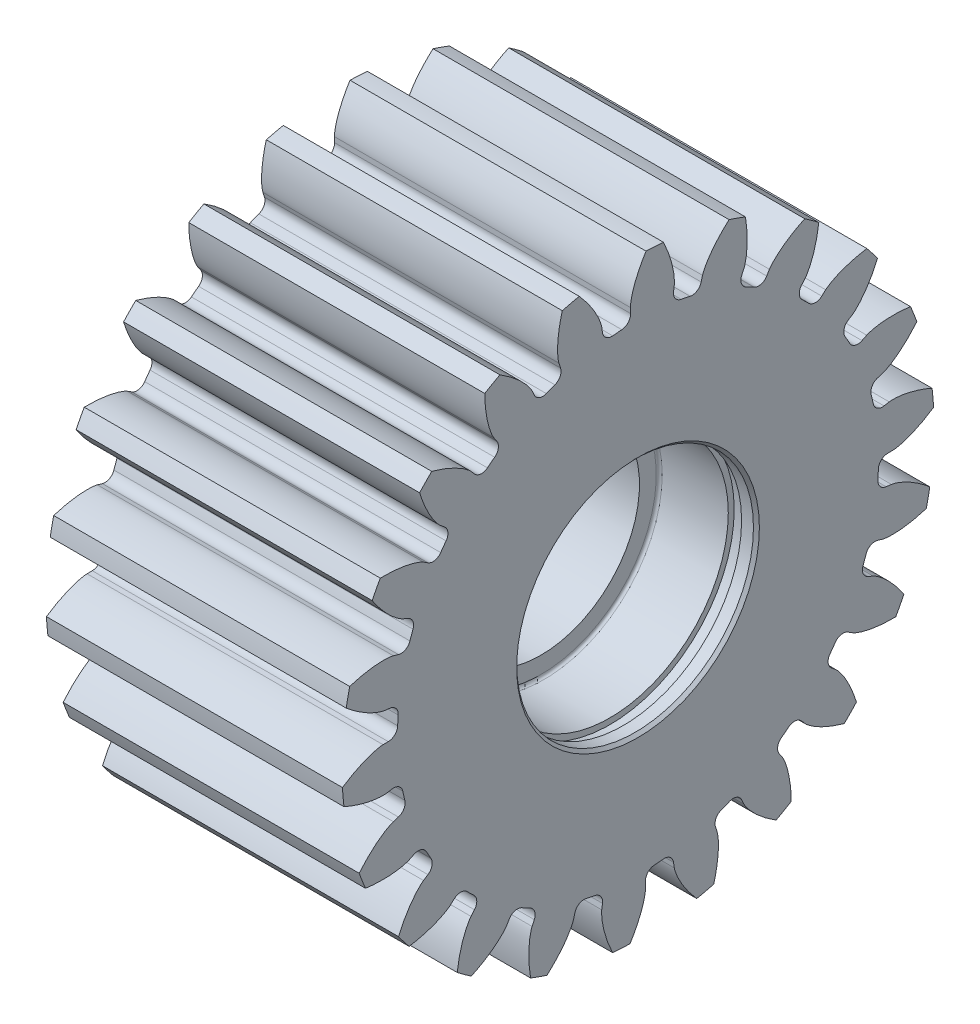
SolidWorks part; units mm, degrees
material "1.7225 (42CrMo4)"
ref_plane "前基準面" through (0, 0, 0) normal (0, 0, 1) x (1, 0, 0)
ref_plane "上基準面" through (0, 0, 0) normal (0, 1, 0) x (1, 0, 0)
ref_plane "右基準面" through (0, 0, 0) normal (1, 0, 0) x (0, 0, -1)
sketch "InvoluteProfile" plane through (0, 0, 0) normal (1, 0, 0) x (0, 0, -1)
  spline S0 degree 4 poles (25.8415, 0) (25.8533, 0.0002) (25.8864, 0.0014) (25.9488, 0.0059) (26.0504, 0.0168) (26.1794, 0.0356) (26.3456, 0.0657) (26.5403, 0.1083) (26.7532, 0.1629) (26.9832, 0.2304) (27.2112, 0.3049) (27.4372, 0.386) (27.6608, 0.4727) (27.9298, 0.5847) (28.2496, 0.7288) (28.619, 0.9112) (29.0325, 1.1344) (29.4475, 1.3793) (29.8504, 1.6344) (30.2507, 1.908) (30.6332, 2.1841) (31.0229, 2.4868) (31.3789, 2.7743) (31.7687, 3.1138) (32.0807, 3.3927) (32.4822, 3.7787) (32.7163, 4.0121) (32.9866, 4.2912) (33.1047, 4.4184) (33.1775, 4.4966) knots 0 0 0 0 0 0.005377 0.015084 0.028532 0.04661 0.064855 0.092111 0.119476 0.146842 0.174209 0.201575 0.228941 0.256307 0.307035 0.361767 0.4165 0.471232 0.525964 0.580697 0.635429 0.690161 0.744894 0.799626 0.854358 0.909091 0.954545 1 1 1 1 1 construction
  spline S1 degree 4 poles (25.8415, 0) (25.8533, 0.0002) (25.8864, 0.0014) (25.9488, 0.0059) (26.0504, 0.0168) (26.1794, 0.0356) (26.3456, 0.0657) (26.5403, 0.1083) (26.7532, 0.1629) (26.9832, 0.2304) (27.2112, 0.3049) (27.4372, 0.386) (27.6608, 0.4727) (27.9298, 0.5847) (28.2496, 0.7288) (28.619, 0.9112) (29.0325, 1.1344) (29.4475, 1.3793) (29.8504, 1.6344) (30.2507, 1.908) (30.6332, 2.1841) (31.0229, 2.4868) (31.3789, 2.7743) (31.7687, 3.1138) (32.0807, 3.3927) (32.3951, 3.695) (32.547, 3.8442) (32.6241, 3.9214) knots 0 0 0 0 0 0.005377 0.015084 0.028532 0.04661 0.064855 0.092111 0.119476 0.146842 0.174209 0.201575 0.228941 0.256307 0.307035 0.361767 0.4165 0.471232 0.525964 0.580697 0.635429 0.690161 0.744894 0.799626 0.854358 0.909091 0.909091 0.909091 0.909091 0.909091
sketch "Sketch5" plane through (0, 0, 0) normal (1, 0, 0) x (0, 0, -1)
  line L0 (0, 0) -> (21.8279, 0) construction
  line L1 (0, 0) -> (27.4561, -1.5528) construction
  line L2 (25.8415, 0) -> (24.375, 0)
  line L3 (25.6768, -2.9136) -> (24.2196, -2.7483)
  circle A0 centre (0, 0) radius 24.375
  circle A1 centre (0, 0) radius 25.8415
  arc A2 (27.4561, -1.5528) -> (27.4969, 0.4099) centre (0, 0) ccw
  circle A3 centre (0, 0) radius 30
  spline S0 degree 4 poles (-13.4805, 2999.3706) (22.0613, 39.0016) (23.3857, 0.6055) (24.7409, -0.1233) (26.0504, 0.0168) (26.1794, 0.0356) (26.3456, 0.0657) (26.5403, 0.1083) (26.7532, 0.1629) (26.9832, 0.2304) (27.2112, 0.3049) (27.4372, 0.386) (27.6608, 0.4727) (27.9298, 0.5847) (28.2496, 0.7288) (28.619, 0.9112) (29.0325, 1.1344) (29.4475, 1.3793) (29.8504, 1.6344) (30.2507, 1.908) (30.6332, 2.1841) (31.0229, 2.4868) (31.3789, 2.7743) (31.7687, 3.1138) (33.3392, 4.5181) (38.1049, 9.6387) (-24.162, -51.9605) (2152.802, 2125.9545) knots -0.554184 -0.554184 -0.554184 -0.554184 -0.554184 0.005377 0.015084 0.028532 0.04661 0.064855 0.092111 0.119476 0.146842 0.174209 0.201575 0.228941 0.256307 0.307035 0.361767 0.4165 0.471232 0.525964 0.580697 0.635429 0.690161 0.744894 0.799626 0.854358 1.792198 1.792198 1.792198 1.792198 1.792198 only from (25.8415, 0) to (32.6241, 3.9214) construction
  spline S1 degree 4 poles (25.8415, 0) (25.8533, 0.0002) (25.8864, 0.0014) (25.9488, 0.0059) (26.0504, 0.0168) (26.1794, 0.0356) (26.3456, 0.0657) (26.5403, 0.1083) (26.7532, 0.1629) (26.9832, 0.2304) (27.2112, 0.3049) (27.4372, 0.386) (27.6608, 0.4727) (27.9298, 0.5847) (28.2496, 0.7288) (28.619, 0.9112) (29.0325, 1.1344) (29.4475, 1.3793) (29.8504, 1.6344) (30.2507, 1.908) (30.6332, 2.1841) (31.0229, 2.4868) (31.3789, 2.7743) (31.7687, 3.1138) (32.0807, 3.3927) (32.3951, 3.695) (32.547, 3.8442) (32.6241, 3.9214) knots 0 0 0 0 0 0.005377 0.015084 0.028532 0.04661 0.064855 0.092111 0.119476 0.146842 0.174209 0.201575 0.228941 0.256307 0.307035 0.361767 0.4165 0.471232 0.525964 0.580697 0.635429 0.690161 0.744894 0.799626 0.854358 0.909091 0.909091 0.909091 0.909091 0.909091
  spline S2 degree 4 poles (25.6768, -2.9136) (25.6885, -2.9152) (25.7212, -2.92) (25.7826, -2.9316) (25.8823, -2.9539) (26.0084, -2.9871) (26.1702, -3.0357) (26.3589, -3.1001) (26.5642, -3.1783) (26.7852, -3.2713) (27.0033, -3.3711) (27.2187, -3.4771) (27.4311, -3.5884) (27.6857, -3.7301) (27.9873, -3.9093) (28.3337, -4.1322) (28.7194, -4.4006) (29.1042, -4.6907) (29.4758, -4.9896) (29.8427, -5.3066) (30.1916, -5.6241) (30.5447, -5.9688) (30.866, -6.2946) (31.215, -6.6758) (31.4936, -6.9882) (31.7719, -7.3241) (31.906, -7.4894) (31.9739, -7.5747) knots 0 0 0 0 0 0.005377 0.015084 0.028532 0.04661 0.064855 0.092111 0.119476 0.146842 0.174209 0.201575 0.228941 0.256307 0.307035 0.361767 0.4165 0.471232 0.525964 0.580697 0.635429 0.690161 0.744894 0.799626 0.854358 0.909091 0.909091 0.909091 0.909091 0.909091
  dimension "D1" = 48.75
  dimension "D2" = 51.6831
  dimension "D3" = 55
  dimension "D4" = 60
  dimension "D5" = 1.9635
sketch "Sketch6" plane through (0, 0, 0) normal (1, 0, 0) x (0, 0, -1)
  circle A0 centre (0, 0) radius 30 construction
  circle A1 centre (0, 0) radius 30
extrude "Boss-Extrude1" add sketch "Sketch6" along normal blind 30
sketch "Sketch7" plane through (30, 0, 0) normal (1, 0, 0) x (0, 0, -1)
  line L0 (25.6768, -2.9136) -> (24.2196, -2.7483) construction
  line L1 (25.8415, 0) -> (24.375, 0) construction
  line L2 (25.6768, -2.9136) -> (24.2196, -2.7483)
  line L3 (25.8415, 0) -> (24.375, 0)
  circle A0 centre (0, 0) radius 30 construction
  circle A1 centre (0, 0) radius 24.375 construction
  arc A2 (29.5682, -5.0718) -> (29.9515, 1.7057) centre (0, 0) ccw
  arc A3 (24.2196, -2.7483) -> (24.375, 0) centre (0, 0) ccw
  spline S0 degree 4 poles (-101.9992, -994.6897) (20.9005, -19.8962) (23.8261, -3.0177) (24.8883, -2.7321) (25.8823, -2.9539) (26.0084, -2.9871) (26.1702, -3.0357) (26.3589, -3.1001) (26.5642, -3.1783) (26.7852, -3.2713) (27.0033, -3.3711) (27.2187, -3.4771) (27.4311, -3.5884) (27.6857, -3.7301) (27.9873, -3.9093) (28.3337, -4.1322) (28.7194, -4.4006) (29.1042, -4.6907) (29.4758, -4.9896) (29.8427, -5.3066) (30.1916, -5.6241) (30.5447, -5.9688) (30.866, -6.2946) (31.215, -6.6758) (32.338, -7.9352) (35.1568, -11.6976) (10.3113, 19.053) (654.231, -790.3422) knots -0.418017 -0.418017 -0.418017 -0.418017 -0.418017 0.005377 0.015084 0.028532 0.04661 0.064855 0.092111 0.119476 0.146842 0.174209 0.201575 0.228941 0.256307 0.307035 0.361767 0.4165 0.471232 0.525964 0.580697 0.635429 0.690161 0.744894 0.799626 0.854358 1.572756 1.572756 1.572756 1.572756 1.572756 only from (25.6768, -2.9136) to (31.9739, -7.5747) construction
  spline S1 degree 4 poles (10.803, 999.8474) (23.0105, 17.4128) (24.0144, 0.3121) (25.0376, -0.0915) (26.0504, 0.0168) (26.1794, 0.0356) (26.3456, 0.0657) (26.5403, 0.1083) (26.7532, 0.1629) (26.9832, 0.2304) (27.2112, 0.3049) (27.4372, 0.386) (27.6608, 0.4727) (27.9298, 0.5847) (28.2496, 0.7288) (28.619, 0.9112) (29.0325, 1.1344) (29.4475, 1.3793) (29.8504, 1.6344) (30.2507, 1.908) (30.6332, 2.1841) (31.0229, 2.4868) (31.3789, 2.7743) (31.7687, 3.1138) (33.0265, 4.2385) (36.2515, 7.6591) (8.0973, -20.0941) (739.1708, 711.5375) knots -0.418017 -0.418017 -0.418017 -0.418017 -0.418017 0.005377 0.015084 0.028532 0.04661 0.064855 0.092111 0.119476 0.146842 0.174209 0.201575 0.228941 0.256307 0.307035 0.361767 0.4165 0.471232 0.525964 0.580697 0.635429 0.690161 0.744894 0.799626 0.854358 1.572756 1.572756 1.572756 1.572756 1.572756 only from (25.8415, 0) to (32.6241, 3.9214) construction
  spline S2 degree 4 poles (25.6768, -2.9136) (25.6885, -2.9152) (25.7212, -2.92) (25.7826, -2.9316) (25.8823, -2.9539) (26.0084, -2.9871) (26.1702, -3.0357) (26.3589, -3.1001) (26.5642, -3.1783) (26.7852, -3.2713) (27.0033, -3.3711) (27.2187, -3.4771) (27.4311, -3.5884) (27.6857, -3.7301) (27.9873, -3.9093) (28.3337, -4.1322) (28.7194, -4.4006) (29.0805, -4.6729) (29.3371, -4.8781) (29.499, -5.0132) (29.5682, -5.0718) knots 0 0 0 0 0 0.005377 0.015084 0.028532 0.04661 0.064855 0.092111 0.119476 0.146842 0.174209 0.201575 0.228941 0.256307 0.307035 0.361767 0.4165 0.471232 0.512483 0.512483 0.512483 0.512483 0.512483
  spline S3 degree 4 poles (25.8415, 0) (25.8533, 0.0002) (25.8864, 0.0014) (25.9488, 0.0059) (26.0504, 0.0168) (26.1794, 0.0356) (26.3456, 0.0657) (26.5403, 0.1083) (26.7532, 0.1629) (26.9832, 0.2304) (27.2112, 0.3049) (27.4372, 0.386) (27.6608, 0.4727) (27.9298, 0.5847) (28.2496, 0.7288) (28.619, 0.9112) (29.0325, 1.1344) (29.4219, 1.3642) (29.7, 1.5392) (29.8761, 1.6552) (29.9515, 1.7057) knots 0 0 0 0 0 0.005377 0.015084 0.028532 0.04661 0.064855 0.092111 0.119476 0.146842 0.174209 0.201575 0.228941 0.256307 0.307035 0.361767 0.4165 0.471232 0.512483 0.512483 0.512483 0.512483 0.512483
extrude "Cut-Extrude1" cut sketch "Sketch7" against normal up to surface (30 mm away) up to face at (0, 0, -30)
fillet "Fillet1" radius 0.95 2 edges at (15, -2.7483, -24.2196) (15, 0, -24.375)
pattern_circular "CirPattern1" count 22 over 360 about axis through (30, 0, 0) along (-1, 0, 0) of "Cut-Extrude1", "Fillet1" reverse direction yes
ref_axis "centerAxis" through (30, 0, 0) along (-1, 0, 0)
sketch "boreSketch" plane through (0, 0, 0) normal (1, 0, 0) x (0, 0, -1)
  circle A0 centre (0, 0) radius 12
  circle A1 centre (0, 0) radius 4.5 construction
  circle A3 centre (0, 0) radius 10
  circle A4 centre (0, 0) radius 5.5 construction
  dimension "D1" = 24
  dimension "D2" = 9
  dimension "D3" = 20
  dimension "D4" = 11
extrude "shaftAxis" cut sketch "boreSketch" along normal up to surface (30 mm away) contours A3 region at (0, 0, 0) up to face at (30, 0, 0)
extrude "bearingHousing" cut sketch "Sketch8<3>" along normal blind 9.85
sketch "Sketch8<3>" plane through (0, 0, 0) normal (1, 0, 0) x (0, 0, -1) same geometry as "boreSketch"
fillet "housingFillet" radius 0.3 1 edges at (9.85, 0, -12)
sketch "retainingRingSketch" plane through (0, 0, 0) normal (1, 0, 0) x (0, 0, -1)
  circle A0 centre (0, 0) radius 12.6
  dimension "D1" = 25.2
extrude "retainingRingSlot" cut sketch "retainingRingSketch" along normal blind 1.35 from offset 1.5
ref_plane "midPlane" through (15, 0, 0) normal (-1, 0, 0) x (0, 0, 1)
mirror "Mirror1" about plane through (15, 0, 0) normal (-1, 0, 0) of "bearingHousing", "retainingRingSlot", "housingFillet"
chamfer "Chamfer2" distance 0.3 angle 45 2 edges at (30, 0, -12) (0, 0, -12)
equation "\"a\"= 20"
equation "\"M\"= 2.5"
equation "\"T\"= 22"
equation "\"R\"= 0.38 * \"M\""
equation "\"D\"= \"M\" * \"T\""
equation "\"Da\"= ( \"T\" + 2 ) * \"M\""
equation "\"Df\"= ( \"T\" - 2.5 ) * \"M\""
equation "\"Db\"= \"M\" * \"T\" * cos ( \"a\" )"
equation "\"rb\"= \"Db\" / 2"
equation "\"S\"= pi * \"M\" * 0.5"
equation "\"D1@Sketch5\"=\"Df\""
equation "\"D2@Sketch5\"=\"Db\""
equation "\"D3@Sketch5\"=\"D\""
equation "\"D4@Sketch5\"=\"Da\""
equation "\"D5@Sketch5\"=\"S\"/2"
equation "\"D1@Fillet1\"=\"R\""
equation "\"D1@CirPattern1\"=\"T\""
